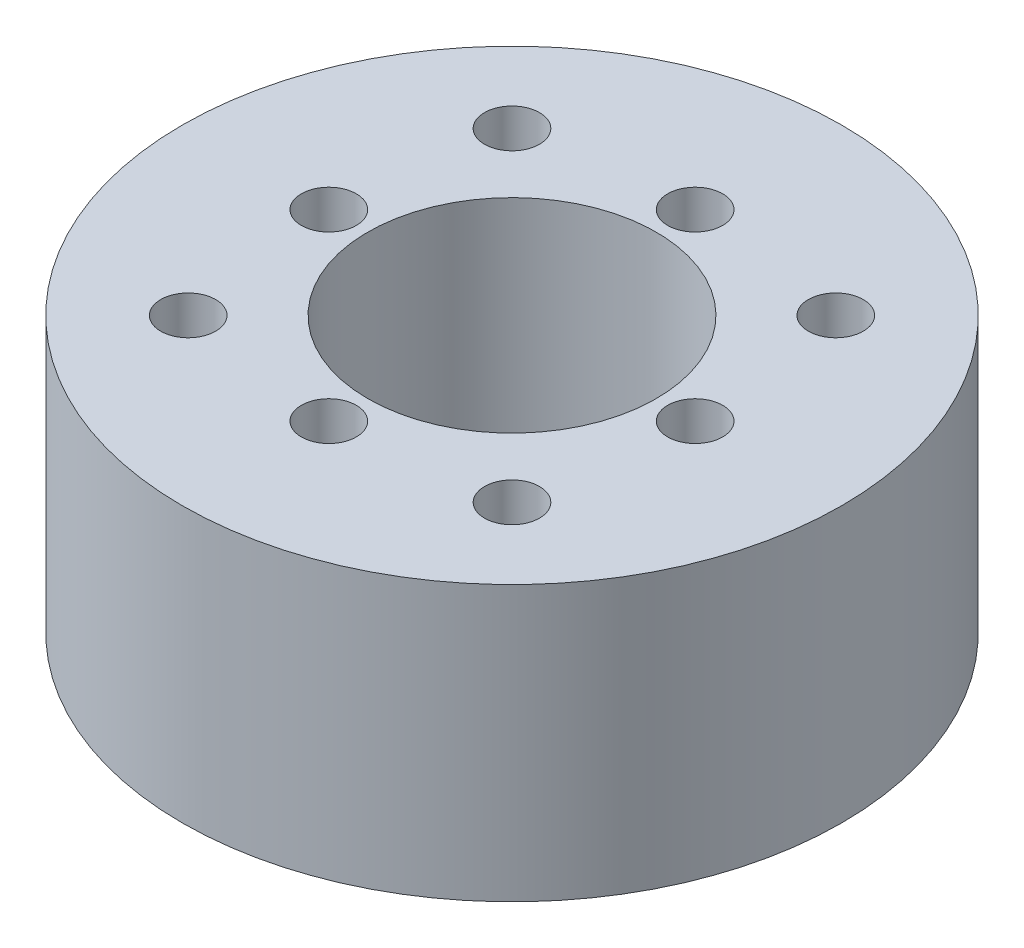
SolidWorks part; units mm, degrees
ref_plane "前视基准面" through (0, 0, 0) normal (0, 0, 1) x (1, 0, 0)
ref_plane "上视基准面" through (0, 0, 0) normal (0, 1, 0) x (1, 0, 0)
ref_plane "右视基准面" through (0, 0, 0) normal (1, 0, 0) x (0, 0, -1)
other "Configuration Table"
sketch "Sketch1" plane through (0, 0, 0) normal (0, 1, 0) x (1, 0, 0)
  circle A0 centre (0, 0) radius 36
  dimension "D1" = 72
extrude "Boss-Extrude1" add sketch "Sketch1" along normal blind 30 contours A0
sketch "Sketch2" plane through (0, 30, 0) normal (0, 1, 0) x (1, 0, 0)
  circle A0 centre (20, 0) radius 3
  circle A1 centre (0, -20) radius 3
  circle A2 centre (-20, 0) radius 3
  circle A3 centre (0, 20) radius 3
  point P12 (0, 0)
  dimension "D3" = 6
  dimension "D1" = 20
  dimension "D2" = 4
extrude "Cut-Extrude1" cut sketch "Sketch2" against normal blind 30
ref_axis "Axis1" through (0, 30, 0) along (0, -1, 0)
sketch "Sketch4" plane through (0, 30, 0) normal (0, 1, 0) x (1, 0, 0)
  line L0 (0, 0) -> (17.6777, 17.6777) construction
  line L1 (0, 0) -> (20, 0) construction
  circle A0 centre (17.6777, 17.6777) radius 3
  circle A1 centre (17.6777, -17.6777) radius 3
  circle A2 centre (-17.6777, -17.6777) radius 3
  circle A3 centre (-17.6777, 17.6777) radius 3
  point P15 (0, 0)
  dimension "D1" = 6
  dimension "D2" = 25
  dimension "D3" = 45
  dimension "D4" = 4
extrude "Cut-Extrude2" cut sketch "Sketch4" against normal blind 30
sketch "Sketch5" plane through (0, 30, 0) normal (0, 1, 0) x (1, 0, 0)
  circle A0 centre (0, 0) radius 15.75
  dimension "D1" = 31.5
extrude "Cut-Extrude3" cut sketch "Sketch5" against normal blind 30
